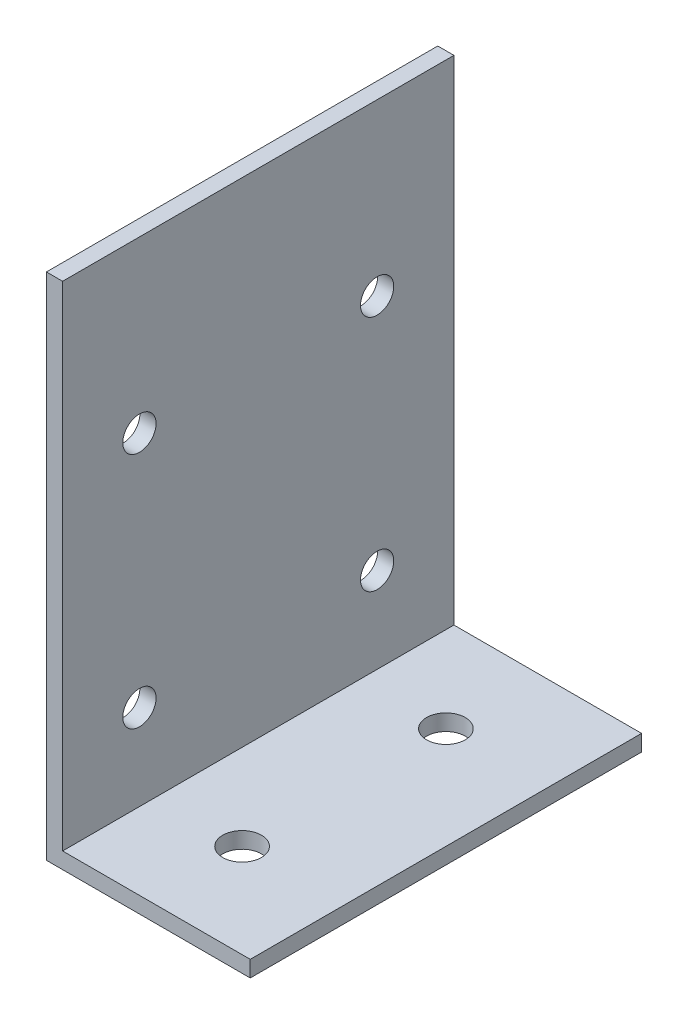
SolidWorks part; units mm, degrees
ref_plane "Front Plane" through (0, 0, 0) normal (0, 0, 1) x (1, 0, 0)
ref_plane "Top Plane" through (0, 0, 0) normal (0, 1, 0) x (1, 0, 0)
ref_plane "Right Plane" through (0, 0, 0) normal (1, 0, 0) x (0, 0, -1)
sketch "Sketch1" plane through (0, 0, 0) normal (0, 0, 1) x (1, 0, 0)
  line L0 (0, 50) -> (0, 0)
  line L1 (0, 0) -> (20, 0)
  line L2 (1.5875, 50) -> (1.5875, 1.5875)
  line L3 (1.5875, 1.5875) -> (20, 1.5875)
  line L4 (0, 50) -> (1.5875, 50)
  line L5 (20, 1.5875) -> (20, 0)
  dimension "D1" = 50
  dimension "D2" = 20
  dimension "D3" = 1.5875
extrude "Boss-Extrude1" add sketch "Sketch1" along normal blind 19.2
hole_wizard "#4 Clearance Hole1" positions "Sketch3" profile "Sketch2" hole size "#4" standard "ANSI Inch" end condition through all
sketch "Sketch3" plane through (0, 0, 0) normal (-1, 0, 0) x (0, 0, 1)
  line L0 (0, 50) -> (0, 0) construction
  line L1 (19.2, 0) -> (0, 0) construction
  point P0 (11.6625, 33.325)
  point P2 (11.6625, 10)
  dimension "D1" = 11.6625
  dimension "D2" = 23.325
  dimension "D3" = 10
sketch "Sketch2" plane through (0, 33.325, 11.6625) normal (0, 1, 0) x (0, 0, 1)
  line L0 (0, 0) -> (0, 20)
  line L1 (0, 20) -> (1.6319, 20)
  line L2 (1.6319, 20) -> (1.6319, 0)
  line L5 (1.6319, 0) -> (0, 0)
  line L11 (0, -6.35) -> (0, 107.95) construction
  dimension "Thru Hole Dia." = 3.2639
  dimension "Thru Hole Depth" = 20
hole_wizard "#6 Clearance Hole1" positions "3DSketch1" profile "Sketch4" hole size "#6" standard "ANSI Inch" end condition through all
sketch3d "3DSketch1"
  line L0 (0, 0, 0) -> (20, 0, 0) construction
  line L1 (20, 0, 19.2) -> (20, 0, 0) construction
  point P0 (10, 0, 10)
  dimension "D1" = 10
  dimension "D2" = 10
sketch "Sketch4" plane through (10, 0, 10) normal (1, 0, 0) x (0, 0, -1)
  line L0 (0, 0) -> (0, 50)
  line L1 (0, 50) -> (1.8986, 50)
  line L2 (1.8986, 50) -> (1.8986, 0)
  line L5 (1.8986, 0) -> (0, 0)
  line L11 (0, -6.35) -> (0, 107.95) construction
  dimension "Thru Hole Dia." = 3.7973
  dimension "Thru Hole Depth" = 50
mirror "Mirror1" about plane through (0, 0, 0) normal (0, 0, -1) of "#6 Clearance Hole1", "#4 Clearance Hole1", "Boss-Extrude1"
